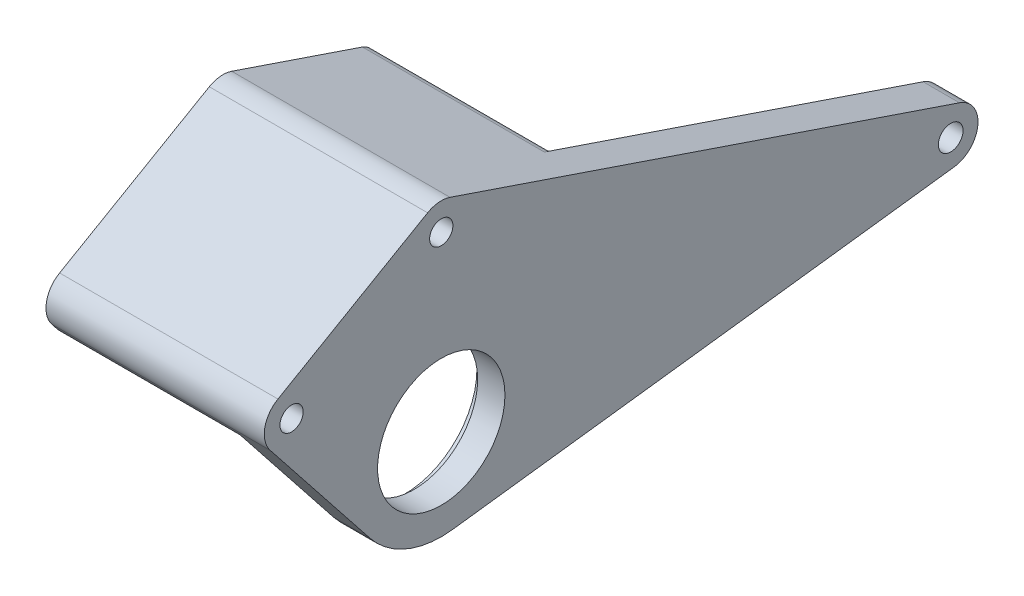
SolidWorks part; units mm, degrees
ref_plane "Front Plane" through (0, 0, 0) normal (0, 0, 1) x (1, 0, 0)
ref_plane "Top Plane" through (0, 0, 0) normal (0, 1, 0) x (1, 0, 0)
ref_plane "Right Plane" through (0, 0, 0) normal (1, 0, 0) x (0, 0, -1)
sketch "Sketch1" plane through (0, 0, 0) normal (1, 0, 0) x (0, 0, -1)
  line L0 (1.5302, 4.51) -> (-87.3698, 34.6725)
  line L1 (-91.2812, 34.2869) -> (-117.4027, 19.2057)
  line L2 (-118.7548, 12.1242) -> (-101.3443, -9.8568)
  line L3 (-86.9156, -15.7505) -> (0.5953, -4.7251)
  line L4 (-115.0215, 15.0813) -> (-88.9, 0) construction
  line L5 (-88.9, 0) -> (-88.9, 30.1625) construction
  line L6 (0, 0) -> (-88.9, 0) construction
  circle A0 centre (0, 0) radius 2.159
  arc A1 (0.5953, -4.7251) -> (1.5302, 4.51) centre (0, 0) ccw
  arc A2 (-87.3698, 34.6725) -> (-91.2812, 34.2869) centre (-88.9, 30.1625) ccw
  arc A3 (-117.4027, 19.2057) -> (-118.7548, 12.1242) centre (-115.0215, 15.0813) ccw
  arc A4 (-101.3443, -9.8568) -> (-86.9156, -15.7505) centre (-88.9, 0) ccw
  circle A5 centre (-88.9, 0) radius 11.1125
  circle A6 centre (-88.9, 30.1625) radius 2.032
  circle A7 centre (-88.9, 0) radius 25.4 construction
  circle A8 centre (-115.0215, 15.0813) radius 2.032
  dimension "D1" = 4.318
  dimension "D2" = 9.525
  dimension "D3" = 22.225
  dimension "D4" = 4.7625
  dimension "D5" = 15.875
  dimension "D6" = 50.8
  dimension "D10" = 4.064
  dimension "D7" = 30.1625
  dimension "D8" = 88.9
  dimension "D9" = 60
extrude "Boss-Extrude1" add sketch "Sketch1" along normal blind 6.35
sketch "Sketch2" plane through (6.35, 0, 0) normal (1, 0, 0) x (0, 0, -1)
  circle A0 centre (-88.9, 0) radius 12.573
  dimension "D1" = 25.146
extrude "Cut-Extrude1" cut sketch "Sketch2" against normal blind 1.5875
sketch "Sketch3" plane through (6.35, 0, 0) normal (1, 0, 0) x (0, 0, -1)
  line L0 (-91.2812, 34.2869) -> (-117.4027, 19.2057) construction
  line L1 (-88.9, 33.902) -> (-92.1385, 32.0322)
  line L2 (-92.1385, 32.0322) -> (-92.1385, 28.2928)
  line L3 (-92.1385, 28.2928) -> (-88.9, 26.423)
  line L4 (-88.9, 26.423) -> (-85.6615, 28.2928)
  line L5 (-85.6615, 28.2928) -> (-85.6615, 32.0322)
  line L6 (-85.6615, 32.0322) -> (-88.9, 33.902)
  line L7 (-115.0215, 18.8207) -> (-118.26, 16.951)
  line L8 (-118.26, 16.951) -> (-118.26, 13.2115)
  line L9 (-118.26, 13.2115) -> (-115.0215, 11.3418)
  line L10 (-115.0215, 11.3418) -> (-111.783, 13.2115)
  line L11 (-111.783, 13.2115) -> (-111.783, 16.951)
  line L12 (-111.783, 16.951) -> (-115.0215, 18.8207)
  line L13 (-91.2812, 34.2869) -> (-117.4027, 19.2057)
  line L14 (-118.7548, 12.1242) -> (-114.2807, 6.4756)
  line L15 (-118.7548, 12.1242) -> (-101.3443, -9.8568) construction
  line L16 (-87.3698, 34.6725) -> (-57.3033, 24.4713)
  line L17 (1.5302, 4.51) -> (-87.3698, 34.6725) construction
  line L18 (-70.0469, 18.1844) -> (-57.3033, 24.4713)
  circle A0 centre (-88.9, 30.1625) radius 3.2385 construction
  circle A1 centre (-115.0215, 15.0813) radius 3.2385 construction
  arc A2 (-87.3698, 34.6725) -> (-91.2812, 34.2869) centre (-88.9, 30.1625) ccw construction
  arc A3 (-117.4027, 19.2057) -> (-118.7548, 12.1242) centre (-115.0215, 15.0813) ccw construction
  arc A4 (-87.3698, 34.6725) -> (-91.2812, 34.2869) centre (-88.9, 30.1625) ccw
  arc A5 (-117.4027, 19.2057) -> (-118.7548, 12.1242) centre (-115.0215, 15.0813) ccw
  arc A6 (-114.2807, 6.4756) -> (-70.0469, 18.1844) centre (-88.9, 0) cw
  dimension "D4" = 26.1937
  dimension "D1" = 6.477
  dimension "D2" = 6.477
  dimension "D3" = 31.75
  dimension "D5" = 45
extrude "Boss-Extrude2" add sketch "Sketch3" along normal blind 31.75
fillet "Fillet1" radius 3.175 3 edges at (22.225, 24.4713, 57.3033) (22.225, 18.1844, 70.0469) (22.225, 6.4756, 114.2807)
mirror "Mirror1" about plane through (6.35, 0, 0) normal (1, 0, 0) of bodies 104 102
delete or keep bodies "Body-Delete/Keep 1" type delete bodies bodies 104
